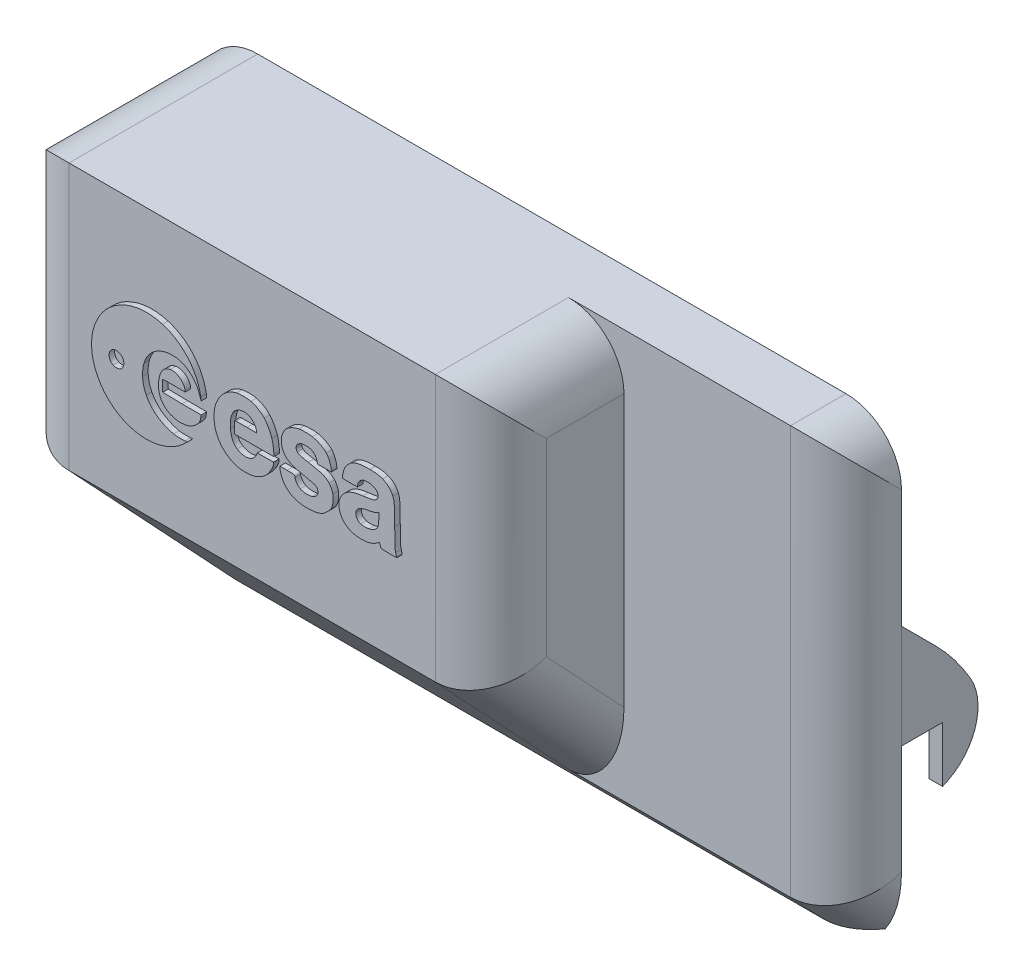
SolidWorks part; units mm, degrees
material "PLA"
ref_plane "Front Plane" through (0, 0, 0) normal (0, 0, 1) x (1, 0, 0)
ref_plane "Top Plane" through (0, 0, 0) normal (0, 1, 0) x (1, 0, 0)
ref_plane "Right Plane" through (0, 0, 0) normal (1, 0, 0) x (0, 0, -1)
sketch "Sketch1" plane through (0, 0, 0) normal (0, 1, 0) x (1, 0, 0)
  line L1 (0, 0) -> (-63, 0)
  line L2 (0, 0) -> (0, -17)
  line L3 (0, -17) -> (-63, -17)
  line L4 (-63, 0) -> (-63, -17)
  dimension "D1" = 63
  dimension "D2" = 17
extrude "Boss-Extrude1" add sketch "Sketch1" along normal blind 40
sketch "Sketch3" plane through (0, 40, 0) normal (0, 1, 0) x (1, 0, 0)
  line L0 (-63, -17) -> (0, -17) construction
  line L1 (-20, -17) -> (0, -17)
  line L2 (-20, -17) -> (-20, -5)
  line L3 (-20, -5) -> (0, -5)
  line L4 (0, -17) -> (0, -5)
  line L6 (0, -17) -> (0, 0) construction
  line L7 (0, 0) -> (-63, 0) construction
  dimension "D1" = 20
  dimension "D2" = 5
extrude "Cut-Extrude1" cut sketch "Sketch3" against normal up to next
chamfer "Chamfer1" distance 15 distance2 16 1 edges at (-41.5, 0, 17) first distance on face at (-27.6667, 0, 7.3333)
fillet "Fillet4" radius 5 9 edges at (0, 1.6, 3.5) (-63, 8, 9.5) (-63, 28, 17) (0, 40, 2.5) (-63, 40, 8.5) (0, 21.6, 5) (-20, 40, 11) (-20, 9.6, 11) (-20, 28, 17)
shell "Shell1" thickness 1.2 removed face at (-31.5, 20.2497, 0)
sketch "Sketch2" plane through (0, 0, 0) normal (1, 0, 0) x (0, 0, -1)
  line L0 (0, 24.3569) -> (8.7, 15.6569)
  line L1 (0, 35) -> (0, 5.1772) construction
  line L2 (8.7, 15.6569) -> (8.7, 10)
  line L3 (8.7, 10) -> (3.7, 10)
  line L4 (3.7, 10) -> (3.7, 15)
  line L6 (3.7, 15) -> (6.5284, 17.8284) construction
  line L7 (0, 24.3569) -> (0, 15)
  line L8 (0, 15) -> (3.7, 15)
  dimension "D1" = 3.7
  dimension "D2" = 5
  dimension "D3" = 45
  dimension "D4" = 5
  dimension "D5" = 25
  dimension "D6" = 4
extrude "Boss-Extrude2" add sketch "Sketch2" against normal blind 1.2 contours L0 L2 L3 L4 L8 L7
fillet "Fillet2" radius 20 1 edges at (-0.6, 15.6569, -8.7)
fillet "Fillet3" radius 5 1 edges at (-0.6, 10, -8.7)
pattern_linear "LPattern1" [suppressed] count 2 spacing 30 of bodies 102
ref_plane "Plane1" through (-31.5, 0, 0) normal (1, 0, 0) x (0, 0, -1)
mirror "Mirror1" about plane through (-31.5, 0, 0) normal (1, 0, 0) of "Boss-Extrude2", "Fillet2", "Fillet3", "LPattern1"
sketch "Sketch4" plane through (0, 0, 17) normal (0, 0, 1) x (1, 0, 0)
  line L8 (-45.6351, 26.5432) -> (-45.5956, 26.786)
  line L9 (-45.5956, 26.786) -> (-47.3103, 26.7934)
  line L10 (-48.0353, 27.8576) -> (-47.0342, 27.8576)
  line L11 (-47.0342, 27.8576) -> (-47.051, 27.9992)
  line L12 (-38.4865, 26.151) -> (-38.5062, 26.3431)
  line L13 (-38.5062, 26.3431) -> (-37.8469, 26.3431)
  line L14 (-33.8691, 28.3017) -> (-33.8691, 28.2005)
  line L15 (-33.8691, 28.2005) -> (-34.4945, 28.2005)
  line L16 (-34.4945, 28.2005) -> (-35.1199, 28.2005)
  line L17 (-35.1199, 28.2005) -> (-35.1398, 28.3362)
  line L26 (-39.0471, 26.9893) -> (-39.0555, 26.8146)
  line L27 (-39.0555, 26.8146) -> (-40.82, 26.8073)
  line L28 (-40.82, 26.8073) -> (-42.5845, 26.7999)
  line L29 (-42.5845, 26.7999) -> (-42.5845, 27.3251)
  line L30 (-42.5845, 27.3251) -> (-42.5845, 27.8502)
  line L31 (-42.5845, 27.8502) -> (-42.4431, 27.869)
  line L32 (-41.4501, 27.8859) -> (-40.5985, 27.8841)
  line L33 (-40.5985, 27.8841) -> (-40.6046, 28.006)
  line L34 (-40.584, 26.2226) -> (-40.5328, 26.3574)
  line L35 (-40.5328, 26.3574) -> (-39.8013, 26.3651)
  line L36 (-39.8013, 26.3651) -> (-39.0698, 26.3727)
  line L37 (-39.0698, 26.3727) -> (-39.0698, 26.2767)
  line L48 (-31.4937, 28.3817) -> (-31.5117, 28.2148)
  line L49 (-31.5117, 28.2148) -> (-32.1669, 28.2071)
  line L50 (-27.9906, 24.5215) -> (-27.976, 24.4572)
  line L51 (-27.976, 24.4572) -> (-28.6645, 24.4572)
  line L52 (-29.4817, 24.7351) -> (-29.5299, 24.8845)
  line L53 (-29.5299, 24.8845) -> (-29.6778, 24.7735)
  line L58 (-29.5889, 26.6824) -> (-29.5749, 27.1789)
  line L59 (-29.5749, 27.1789) -> (-29.7003, 27.1059)
  spline S32 degree 3 poles (-50.0099, 22.4579) (-49.1716, 22.5415) (-48.2548, 22.8942) (-47.5987, 23.3856) knots 0 0 0 0 1 1 1 1
  spline S33 degree 3 poles (-47.5987, 23.3856) (-47.2936, 23.6141) (-46.8707, 23.9899) (-46.8707, 24.0326) knots 0 0 0 0 1 1 1 1
  spline S34 degree 3 poles (-46.8707, 24.0326) (-46.8707, 24.0509) (-46.9298, 24.0535) (-47.035, 24.0397) knots 0 0 0 0 1 1 1 1
  spline S35 degree 3 poles (-47.035, 24.0397) (-47.2963, 24.0054) (-47.8374, 24.0215) (-48.0709, 24.0705) knots 0 0 0 0 1 1 1 1
  spline S36 degree 3 poles (-48.0709, 24.0705) (-49.1914, 24.3056) (-50.0925, 24.9618) (-50.5438, 25.8711) knots 0 0 0 0 1 1 1 1
  spline S37 degree 3 poles (-50.5438, 25.8711) (-50.762, 26.3108) (-50.8454, 26.6473) (-50.8638, 27.1629) knots 0 0 0 0 1 1 1 1
  spline S38 degree 3 poles (-50.8638, 27.1629) (-50.88, 27.6156) (-50.8477, 27.9068) (-50.7398, 28.279) knots 0 0 0 0 1 1 1 1
  spline S39 degree 3 poles (-50.7398, 28.279) (-50.4711, 29.2064) (-49.7258, 29.8898) (-48.7493, 30.1042) knots 0 0 0 0 1 1 1 1
  spline S40 degree 3 poles (-48.7493, 30.1042) (-48.4705, 30.1654) (-47.9181, 30.1666) (-47.6475, 30.1066) knots 0 0 0 0 1 1 1 1
  spline S41 degree 3 poles (-47.6475, 30.1066) (-46.9739, 29.9571) (-46.3626, 29.4975) (-45.9836, 28.8558) knots 0 0 0 0 1 1 1 1
  spline S42 degree 3 poles (-45.9836, 28.8558) (-45.8687, 28.6612) (-45.7385, 28.3402) (-45.654, 28.0433) knots 0 0 0 0 1 1 1 1
  spline S43 degree 3 poles (-45.654, 28.0433) (-45.5797, 27.7822) (-45.566, 27.8501) (-45.6252, 28.1862) knots 0 0 0 0 1 1 1 1
  spline S44 degree 3 poles (-45.6252, 28.1862) (-45.959, 30.079) (-47.2745, 31.5825) (-49.071, 32.1244) knots 0 0 0 0 1 1 1 1
  spline S45 degree 3 poles (-49.071, 32.1244) (-51.4088, 32.8295) (-53.9068, 31.741) (-54.9608, 29.5578) knots 0 0 0 0 1 1 1 1
  spline S46 degree 3 poles (-54.9608, 29.5578) (-55.2426, 28.9742) (-55.3838, 28.4749) (-55.4459, 27.8428) knots 0 0 0 0 1 1 1 1
  spline S47 degree 3 poles (-55.4459, 27.8428) (-55.5354, 26.9311) (-55.3676, 26.0443) (-54.9431, 25.1858) knots 0 0 0 0 1 1 1 1
  spline S48 degree 3 poles (-54.9431, 25.1858) (-54.0261, 23.3313) (-52.0742, 22.252) (-50.0099, 22.4579) knots 0 0 0 0 1 1 1 1
  spline S49 degree 3 poles (-53.5257, 26.7328) (-54.1144, 27.0261) (-53.9579, 27.9136) (-53.3037, 27.9911) knots 0 0 0 0 1 1 1 1
  spline S50 degree 3 poles (-53.3037, 27.9911) (-53.1097, 28.0141) (-52.9297, 27.9599) (-52.7831, 27.8344) knots 0 0 0 0 1 1 1 1
  spline S51 degree 3 poles (-52.7831, 27.8344) (-52.6272, 27.701) (-52.5584, 27.5462) (-52.5584, 27.329) knots 0 0 0 0 1 1 1 1
  spline S52 degree 3 poles (-52.5584, 27.329) (-52.5584, 26.8142) (-53.0639, 26.5026) (-53.5257, 26.7328) knots 0 0 0 0 1 1 1 1
  spline S58 degree 3 poles (-47.1557, 25.2875) (-46.6773, 25.3472) (-46.3373, 25.5124) (-45.9982, 25.8497) knots 0 0 0 0 1 1 1 1
  spline S59 degree 3 poles (-45.9982, 25.8497) (-45.7526, 26.0941) (-45.6881, 26.2172) (-45.6351, 26.5432) knots 0 0 0 0 1 1 1 1
  spline S60 degree 3 poles (-47.3103, 26.7934) (-48.6386, 26.7991) (-49.0301, 26.8088) (-49.0476, 26.8363) knots 0 0 0 0 1 1 1 1
  spline S61 degree 3 poles (-49.0476, 26.8363) (-49.0739, 26.8777) (-49.0793, 27.7456) (-49.0537, 27.8124) knots 0 0 0 0 1 1 1 1
  spline S62 degree 3 poles (-49.0537, 27.8124) (-49.0383, 27.8524) (-48.9217, 27.8576) (-48.0353, 27.8576) knots 0 0 0 0 1 1 1 1
  spline S63 degree 3 poles (-47.051, 27.9992) (-47.1201, 28.5829) (-47.7907, 29.0596) (-48.3814, 28.9449) knots 0 0 0 0 1 1 1 1
  spline S64 degree 3 poles (-48.3814, 28.9449) (-48.831, 28.8576) (-49.086, 28.6273) (-49.2845, 28.1294) knots 0 0 0 0 1 1 1 1
  spline S65 degree 3 poles (-49.2845, 28.1294) (-49.449, 27.7166) (-49.4868, 27.0608) (-49.3719, 26.6146) knots 0 0 0 0 1 1 1 1
  spline S66 degree 3 poles (-49.3719, 26.6146) (-49.1664, 25.817) (-48.4439, 25.2949) (-47.4986, 25.2609) knots 0 0 0 0 1 1 1 1
  spline S67 degree 3 poles (-47.4986, 25.2609) (-47.4432, 25.2589) (-47.2889, 25.2709) (-47.1557, 25.2875) knots 0 0 0 0 1 1 1 1
  spline S74 degree 3 poles (-36.3123, 24.3027) (-36.8135, 24.3513) (-37.1015, 24.4288) (-37.4553, 24.6101) knots 0 0 0 0 1 1 1 1
  spline S75 degree 3 poles (-37.4553, 24.6101) (-37.9913, 24.8849) (-38.4228, 25.5296) (-38.4865, 26.151) knots 0 0 0 0 1 1 1 1
  spline S76 degree 3 poles (-37.8469, 26.3431) (-37.1155, 26.3431) (-37.1833, 26.3623) (-37.1396, 26.1431) knots 0 0 0 0 1 1 1 1
  spline S77 degree 3 poles (-37.1396, 26.1431) (-37.0875, 25.8821) (-36.891, 25.6137) (-36.6695, 25.5012) knots 0 0 0 0 1 1 1 1
  spline S78 degree 3 poles (-36.6695, 25.5012) (-36.3894, 25.3589) (-35.9282, 25.3288) (-35.5965, 25.4312) knots 0 0 0 0 1 1 1 1
  spline S79 degree 3 poles (-35.5965, 25.4312) (-35.3452, 25.5089) (-35.1159, 25.7229) (-35.0844, 25.9092) knots 0 0 0 0 1 1 1 1
  spline S80 degree 3 poles (-35.0844, 25.9092) (-35.0562, 26.0761) (-35.0907, 26.2446) (-35.1731, 26.3425) knots 0 0 0 0 1 1 1 1
  spline S81 degree 3 poles (-35.1731, 26.3425) (-35.2721, 26.4602) (-35.4717, 26.5256) (-36.1332, 26.6573) knots 0 0 0 0 1 1 1 1
  spline S82 degree 3 poles (-36.1332, 26.6573) (-36.9146, 26.813) (-37.2034, 26.8932) (-37.5175, 27.042) knots 0 0 0 0 1 1 1 1
  spline S83 degree 3 poles (-37.5175, 27.042) (-37.8705, 27.2092) (-38.0627, 27.3906) (-38.2135, 27.6986) knots 0 0 0 0 1 1 1 1
  spline S84 degree 3 poles (-38.2135, 27.6986) (-38.3985, 28.0764) (-38.4262, 28.4795) (-38.2963, 28.9001) knots 0 0 0 0 1 1 1 1
  spline S85 degree 3 poles (-38.2963, 28.9001) (-38.2351, 29.098) (-38.0783, 29.3717) (-37.9463, 29.511) knots 0 0 0 0 1 1 1 1
  spline S86 degree 3 poles (-37.9463, 29.511) (-37.6903, 29.781) (-37.231, 30.0166) (-36.7856, 30.1061) knots 0 0 0 0 1 1 1 1
  spline S87 degree 3 poles (-36.7856, 30.1061) (-36.5011, 30.1634) (-35.8658, 30.1634) (-35.5836, 30.1062) knots 0 0 0 0 1 1 1 1
  spline S88 degree 3 poles (-35.5836, 30.1062) (-35.0636, 30.0007) (-34.5854, 29.7556) (-34.3149, 29.4558) knots 0 0 0 0 1 1 1 1
  spline S89 degree 3 poles (-34.3149, 29.4558) (-34.0754, 29.1904) (-33.8691, 28.6564) (-33.8691, 28.3017) knots 0 0 0 0 1 1 1 1
  spline S90 degree 3 poles (-35.1398, 28.3362) (-35.1851, 28.6454) (-35.3804, 28.9116) (-35.6522, 29.0347) knots 0 0 0 0 1 1 1 1
  spline S91 degree 3 poles (-35.6522, 29.0347) (-35.7784, 29.0918) (-35.8438, 29.1006) (-36.1408, 29.1006) knots 0 0 0 0 1 1 1 1
  spline S92 degree 3 poles (-36.1408, 29.1006) (-36.4508, 29.1006) (-36.4988, 29.0935) (-36.6409, 29.0263) knots 0 0 0 0 1 1 1 1
  spline S93 degree 3 poles (-36.6409, 29.0263) (-36.9241, 28.8923) (-37.0559, 28.7091) (-37.0339, 28.4799) knots 0 0 0 0 1 1 1 1
  spline S94 degree 3 poles (-37.0339, 28.4799) (-37.0234, 28.3705) (-36.9997, 28.3188) (-36.925, 28.2417) knots 0 0 0 0 1 1 1 1
  spline S95 degree 3 poles (-36.925, 28.2417) (-36.7883, 28.1007) (-36.5869, 28.0354) (-35.9529, 27.9267) knots 0 0 0 0 1 1 1 1
  spline S96 degree 3 poles (-35.9529, 27.9267) (-34.7792, 27.7255) (-34.3837, 27.5812) (-34.0682, 27.2389) knots 0 0 0 0 1 1 1 1
  spline S97 degree 3 poles (-34.0682, 27.2389) (-33.9328, 27.092) (-33.7768, 26.7742) (-33.7295, 26.5489) knots 0 0 0 0 1 1 1 1
  spline S98 degree 3 poles (-33.7295, 26.5489) (-33.651, 26.1751) (-33.7202, 25.6506) (-33.8899, 25.3337) knots 0 0 0 0 1 1 1 1
  spline S99 degree 3 poles (-33.8899, 25.3337) (-33.9335, 25.2524) (-34.0849, 25.0687) (-34.2263, 24.9255) knots 0 0 0 0 1 1 1 1
  spline S100 degree 3 poles (-34.2263, 24.9255) (-34.5397, 24.6081) (-34.8132, 24.4586) (-35.2392, 24.3716) knots 0 0 0 0 1 1 1 1
  spline S101 degree 3 poles (-35.2392, 24.3716) (-35.5027, 24.3178) (-36.0835, 24.2805) (-36.3123, 24.3027) knots 0 0 0 0 1 1 1 1
  spline S124 degree 3 poles (-42.1987, 24.3566) (-42.9939, 24.5315) (-43.6943, 25.0534) (-44.0708, 25.7513) knots 0 0 0 0 1 1 1 1
  spline S125 degree 3 poles (-44.0708, 25.7513) (-44.3299, 26.2317) (-44.4259, 26.6414) (-44.4269, 27.2718) knots 0 0 0 0 1 1 1 1
  spline S126 degree 3 poles (-44.4269, 27.2718) (-44.4277, 27.7971) (-44.3894, 28.0082) (-44.2081, 28.4781) knots 0 0 0 0 1 1 1 1
  spline S127 degree 3 poles (-44.2081, 28.4781) (-43.8883, 29.3071) (-43.2091, 29.9178) (-42.3987, 30.1051) knots 0 0 0 0 1 1 1 1
  spline S128 degree 3 poles (-42.3987, 30.1051) (-42.0609, 30.1831) (-41.4564, 30.1766) (-41.1129, 30.0911) knots 0 0 0 0 1 1 1 1
  spline S129 degree 3 poles (-41.1129, 30.0911) (-40.6533, 29.9768) (-40.1812, 29.7009) (-39.9017, 29.3833) knots 0 0 0 0 1 1 1 1
  spline S130 degree 3 poles (-39.9017, 29.3833) (-39.6435, 29.0899) (-39.3717, 28.598) (-39.2265, 28.1613) knots 0 0 0 0 1 1 1 1
  spline S131 degree 3 poles (-39.2265, 28.1613) (-39.1364, 27.8902) (-39.0354, 27.2309) (-39.0471, 26.9893) knots 0 0 0 0 1 1 1 1
  spline S132 degree 3 poles (-42.4431, 27.869) (-42.3653, 27.8793) (-41.9185, 27.8869) (-41.4501, 27.8859) knots 0 0 0 0 1 1 1 1
  spline S133 degree 3 poles (-40.6046, 28.006) (-40.6137, 28.1896) (-40.7861, 28.5141) (-40.9553, 28.6662) knots 0 0 0 0 1 1 1 1
  spline S134 degree 3 poles (-40.9553, 28.6662) (-41.13, 28.8233) (-41.2933, 28.902) (-41.5385, 28.9471) knots 0 0 0 0 1 1 1 1
  spline S135 degree 3 poles (-41.5385, 28.9471) (-41.9932, 29.0309) (-42.5276, 28.7908) (-42.7327, 28.4107) knots 0 0 0 0 1 1 1 1
  spline S136 degree 3 poles (-42.7327, 28.4107) (-42.9238, 28.0564) (-43.0076, 27.5474) (-42.9582, 27.0411) knots 0 0 0 0 1 1 1 1
  spline S137 degree 3 poles (-42.9582, 27.0411) (-42.8945, 26.3889) (-42.7093, 26.0049) (-42.3437, 25.7668) knots 0 0 0 0 1 1 1 1
  spline S138 degree 3 poles (-42.3437, 25.7668) (-41.6652, 25.325) (-40.8439, 25.5377) (-40.584, 26.2226) knots 0 0 0 0 1 1 1 1
  spline S139 degree 3 poles (-39.0698, 26.2767) (-39.0698, 25.9883) (-39.3834, 25.4056) (-39.7387, 25.0339) knots 0 0 0 0 1 1 1 1
  spline S140 degree 3 poles (-39.7387, 25.0339) (-40.0349, 24.724) (-40.538, 24.4591) (-41.0192, 24.3597) knots 0 0 0 0 1 1 1 1
  spline S141 degree 3 poles (-41.0192, 24.3597) (-41.2887, 24.3041) (-41.952, 24.3023) (-42.1987, 24.3566) knots 0 0 0 0 1 1 1 1
  spline S162 degree 3 poles (-31.7252, 24.3589) (-32.4659, 24.5195) (-32.9597, 24.9591) (-33.1306, 25.6099) knots 0 0 0 0 1 1 1 1
  spline S163 degree 3 poles (-33.1306, 25.6099) (-33.2755, 26.1618) (-33.1268, 26.6883) (-32.708, 27.106) knots 0 0 0 0 1 1 1 1
  spline S164 degree 3 poles (-32.708, 27.106) (-32.3415, 27.4715) (-31.8336, 27.6694) (-31.0364, 27.7572) knots 0 0 0 0 1 1 1 1
  spline S165 degree 3 poles (-31.0364, 27.7572) (-30.2881, 27.8397) (-29.9815, 27.921) (-29.8127, 28.082) knots 0 0 0 0 1 1 1 1
  spline S166 degree 3 poles (-29.8127, 28.082) (-29.5543, 28.3285) (-29.6012, 28.6864) (-29.9186, 28.8881) knots 0 0 0 0 1 1 1 1
  spline S167 degree 3 poles (-29.9186, 28.8881) (-30.1306, 29.0228) (-30.3191, 29.0658) (-30.6406, 29.0529) knots 0 0 0 0 1 1 1 1
  spline S168 degree 3 poles (-30.6406, 29.0529) (-30.8809, 29.0433) (-30.9421, 29.03) (-31.0868, 28.956) knots 0 0 0 0 1 1 1 1
  spline S169 degree 3 poles (-31.0868, 28.956) (-31.3134, 28.8402) (-31.4679, 28.6222) (-31.4937, 28.3817) knots 0 0 0 0 1 1 1 1
  spline S170 degree 3 poles (-32.1669, 28.2071) (-32.6246, 28.2017) (-32.828, 28.209) (-32.8417, 28.2312) knots 0 0 0 0 1 1 1 1
  spline S171 degree 3 poles (-32.8417, 28.2312) (-32.8984, 28.3229) (-32.7835, 28.8534) (-32.6441, 29.1435) knots 0 0 0 0 1 1 1 1
  spline S172 degree 3 poles (-32.6441, 29.1435) (-32.4991, 29.4454) (-32.1901, 29.7559) (-31.8974, 29.8939) knots 0 0 0 0 1 1 1 1
  spline S173 degree 3 poles (-31.8974, 29.8939) (-31.5034, 30.0796) (-31.1289, 30.1422) (-30.4069, 30.143) knots 0 0 0 0 1 1 1 1
  spline S174 degree 3 poles (-30.4069, 30.143) (-29.8367, 30.1437) (-29.5977, 30.1088) (-29.2524, 29.9745) knots 0 0 0 0 1 1 1 1
  spline S175 degree 3 poles (-29.2524, 29.9745) (-28.8235, 29.8077) (-28.4666, 29.4685) (-28.3244, 29.0928) knots 0 0 0 0 1 1 1 1
  spline S176 degree 3 poles (-28.3244, 29.0928) (-28.1879, 28.7322) (-28.1784, 28.6014) (-28.1557, 26.7718) knots 0 0 0 0 1 1 1 1
  spline S177 degree 3 poles (-28.1557, 26.7718) (-28.135, 25.0974) (-28.1323, 25.0358) (-28.0697, 24.8144) knots 0 0 0 0 1 1 1 1
  spline S178 degree 3 poles (-28.0697, 24.8144) (-28.0342, 24.6886) (-27.9986, 24.5568) (-27.9906, 24.5215) knots 0 0 0 0 1 1 1 1
  spline S179 degree 3 poles (-28.6645, 24.4572) (-29.4501, 24.4572) (-29.3849, 24.435) (-29.4817, 24.7351) knots 0 0 0 0 1 1 1 1
  spline S180 degree 3 poles (-29.6778, 24.7735) (-29.939, 24.5775) (-30.2794, 24.4237) (-30.5975, 24.358) knots 0 0 0 0 1 1 1 1
  spline S181 degree 3 poles (-30.5975, 24.358) (-30.862, 24.3034) (-31.4712, 24.3039) (-31.7252, 24.3589) knots 0 0 0 0 1 1 1 1
  spline S211 degree 3 poles (-30.4687, 25.4695) (-30.2002, 25.5271) (-30.03, 25.6092) (-29.8714, 25.7575) knots 0 0 0 0 1 1 1 1
  spline S212 degree 3 poles (-29.8714, 25.7575) (-29.6433, 25.9709) (-29.6055, 26.0947) (-29.5889, 26.6824) knots 0 0 0 0 1 1 1 1
  spline S213 degree 3 poles (-29.7003, 27.1059) (-29.8356, 27.0271) (-30.2664, 26.9089) (-30.6116, 26.8558) knots 0 0 0 0 1 1 1 1
  spline S214 degree 3 poles (-30.6116, 26.8558) (-30.9134, 26.8094) (-31.2393, 26.7012) (-31.3766, 26.6017) knots 0 0 0 0 1 1 1 1
  spline S215 degree 3 poles (-31.3766, 26.6017) (-31.5254, 26.4939) (-31.6375, 26.303) (-31.6591, 26.1207) knots 0 0 0 0 1 1 1 1
  spline S216 degree 3 poles (-31.6591, 26.1207) (-31.6912, 25.8504) (-31.5076, 25.5778) (-31.2233, 25.4737) knots 0 0 0 0 1 1 1 1
  spline S217 degree 3 poles (-31.2233, 25.4737) (-31.0791, 25.4208) (-30.7055, 25.4188) (-30.4687, 25.4695) knots 0 0 0 0 1 1 1 1
extrude "Boss-Extrude3" add sketch "Sketch4" along normal blind 0.5 contours S47 S48 S32 S33 S34 S35 S36 S37 S38 S39 S40 S41 S42 S43 S44 S45 S46 S51 S52 S49 S50 | S66 S67 S58 S59 L8 L9 S60 S61 S62 L10 L11 S63 S64 S65 | S141 S140 S139 L37 L36 L35 L34 S138 S137 S136 S135 S134 S133 L33 L32 S132 L31 L30 L29 L28 L27 L26 S131 S130 S129 S128 S127 S126 S125 S124 | S101 S100 S99 S98 S97 S96 S95 S94 S93 S92 S91 S90 L17 L16 L15 L14 S89 S88 S87 S86 S85 S84 S83 S82 S81 S80 S79 S78 S77 S76 L13 L12 S75 S74 | S181 S180 L53 L52 S179 L51 L50 S178 S177 S176 S175 S174 S173 S172 S171 S170 L49 L48 S169 S168 S167 S166 S165 S164 S163 S162 S217 S216 S215 S214 S213 L59 L58 S212 S211 region at (-45.7944, 26.1855, 17) region at (-36.0723, 27.1931, 17) region at (-41.7688, 27.2404, 17) region at (-30.4261, 27.1027, 17) region at (-51.6418, 27.5193, 17)
other "Freeze***"
